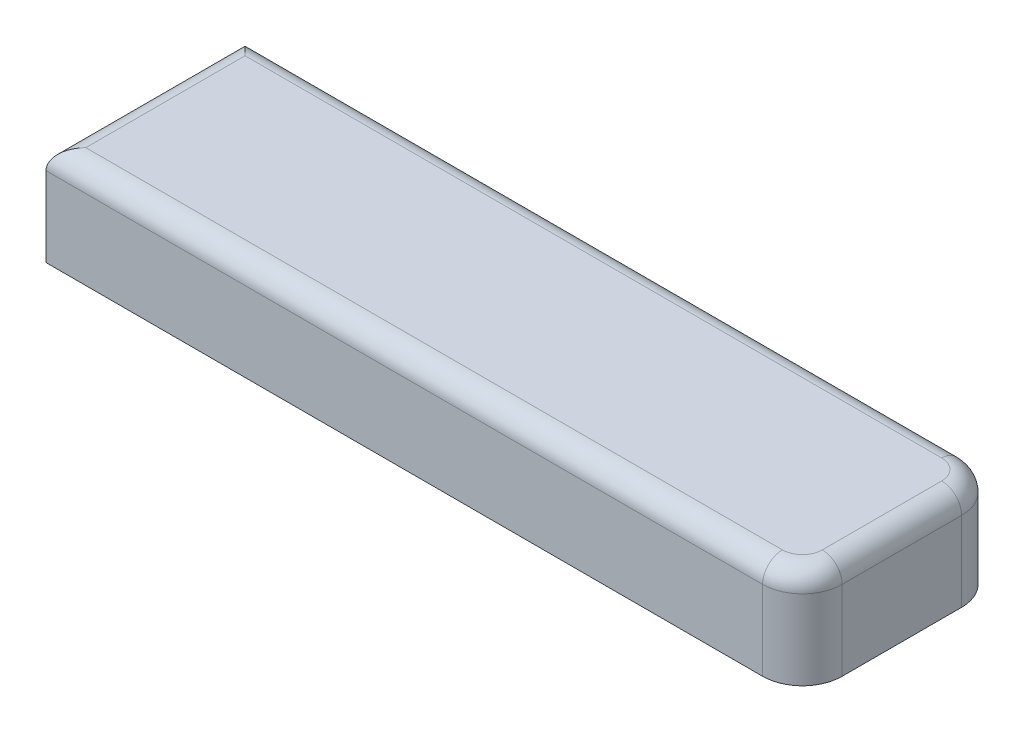
SolidWorks part; units mm, degrees
ref_plane "Piano frontale" through (0, 0, 0) normal (0, 0, 1) x (1, 0, 0)
ref_plane "Piano superiore" through (0, 0, 0) normal (0, 1, 0) x (1, 0, 0)
ref_plane "Piano destro" through (0, 0, 0) normal (1, 0, 0) x (0, 0, -1)
sketch "Schizzo1" plane through (0, 0, 0) normal (0, 0, 1) x (1, 0, 0)
  line L1 (0, 0) -> (38, 0)
  line L2 (0, 0) -> (0, -5)
  line L3 (0, -5) -> (38, -5)
  line L4 (38, 0) -> (38, -5)
  dimension "D1" = 38
  dimension "D2" = 5
extrude "Estrusione-Estrusione1" add sketch "Schizzo1" along normal blind 10
fillet "Raccordo1" radius 1 4 edges at (38, 0, 5) (19, 0, 10) (0, 0, 5) (19, 0, 0)
fillet "Raccordo2" radius 2 4 edges at (37.7071, -0.2929, 9.7071) (37.7071, -0.2929, 0.2929) (38, -3, 0) (38, -3, 10)
